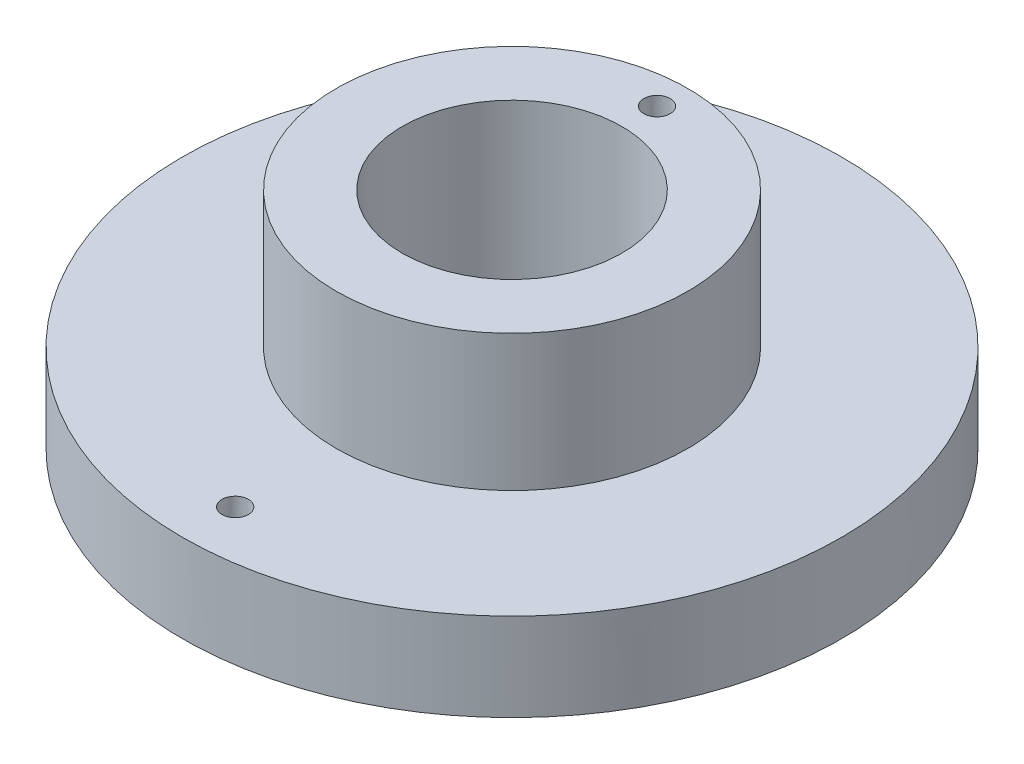
SolidWorks part; units mm, degrees
ref_plane "前视基准面" through (0, 0, 0) normal (0, 0, 1) x (1, 0, 0)
ref_plane "上视基准面" through (0, 0, 0) normal (0, 1, 0) x (1, 0, 0)
ref_plane "右视基准面" through (0, 0, 0) normal (1, 0, 0) x (0, 0, -1)
sketch "草图1" plane through (0, 0, 0) normal (0, 1, 0) x (1, 0, 0)
  line L0 (-20, 0) -> (-20, 31.7214)
  line L1 (20, 0) -> (20, 31.7214)
  arc A0 (20, 31.7214) -> (-20, 31.7214) centre (0, 0) ccw
  arc A1 (-20, 0) -> (20, 0) centre (0, 0) ccw
  dimension "D1" = 75
  dimension "D2" = 40
extrude "凸台-拉伸1" add sketch "草图1" along normal blind 8
sketch "草图2" plane through (0, 8, 0) normal (0, 1, 0) x (1, 0, 0)
  circle A0 centre (0, 0) radius 37.5
  circle A1 centre (0, -31.5) radius 1.5
  dimension "D1" = 3
  dimension "D2" = 31.5
extrude "凸台-拉伸2" add sketch "草图2" along normal blind 10
sketch "草图3" plane through (0, 18, 0) normal (0, 1, 0) x (1, 0, 0)
  circle A0 centre (0, 0) radius 20
  dimension "D1" = 40
extrude "凸台-拉伸3" add sketch "草图3" along normal blind 15.5
sketch "草图4" plane through (0, 33.5, 0) normal (0, 1, 0) x (1, 0, 0)
  circle A0 centre (0, 0) radius 12.5
  dimension "D1" = 25
extrude "切除-拉伸1" cut sketch "草图4" against normal through all
sketch "草图5" plane through (0, 0, 0) normal (0, -1, 0) x (1, 0, 0)
  circle A0 centre (0, -28.5) radius 7.5
  dimension "D1" = 15
  dimension "D2" = 28.5
extrude "切除-拉伸2" cut sketch "草图5" against normal blind 4
fillet "圆角1" radius 4 1 edges at (0, 4, -36)
sketch "草图6" plane through (0, 4, 0) normal (0, -1, 0) x (1, 0, 0)
  circle A0 centre (0, -28.5) radius 1.5
  dimension "D1" = 3
extrude "切除-拉伸3" cut sketch "草图6" against normal blind 5.5
sketch "草图9" plane through (0, 0, 0) normal (0, 0, 1) x (1, 0, 0)
  line L0 (12.5, 33.5) -> (-12.5, 33.5) construction
  circle A0 centre (0, 8) radius 1.5
  dimension "D1" = 3
  dimension "D2" = 25.5
extrude "切除-拉伸4" cut sketch "草图9" against normal blind 30
sketch "草图10" plane through (0, 33.5, 0) normal (0, 1, 0) x (1, 0, 0)
  circle A0 centre (0, 16.5) radius 1.5
  dimension "D1" = 3
  dimension "D2" = 16.5
extrude "切除-拉伸5" cut sketch "草图10" against normal blind 25.5
